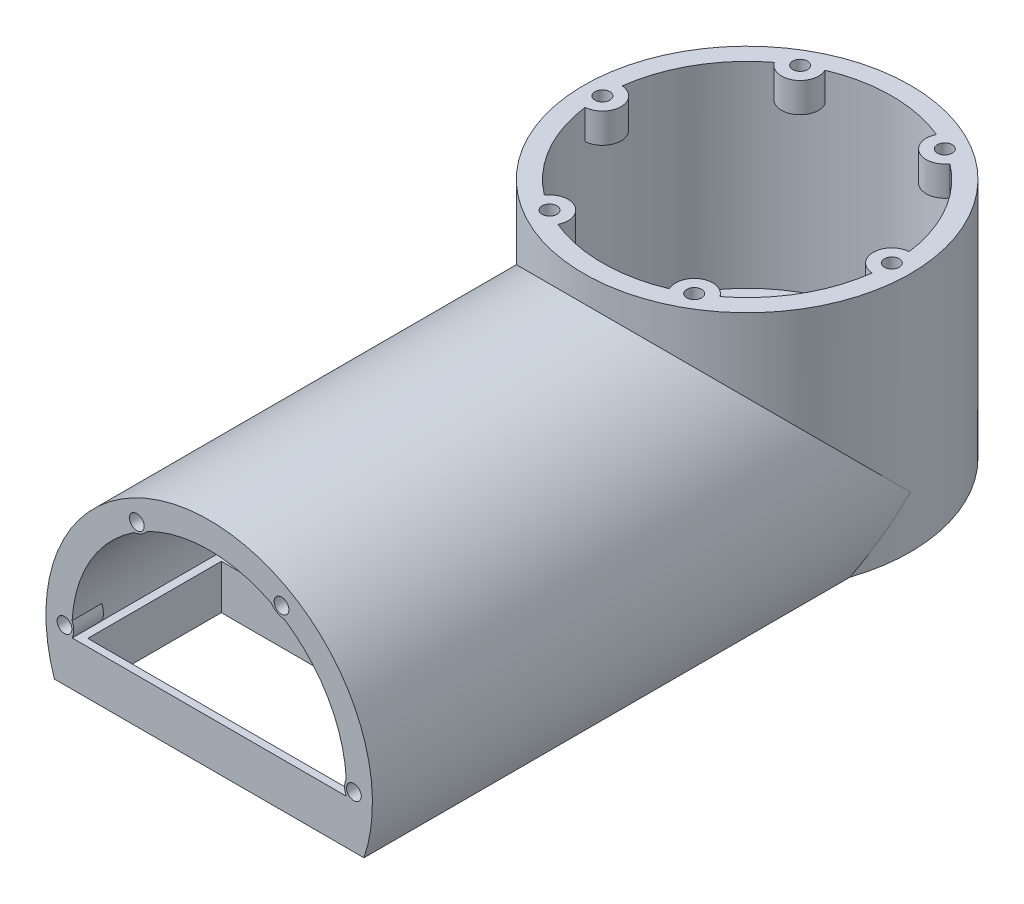
SolidWorks part; units mm, degrees
ref_plane "Спереди" through (0, 0, 0) normal (0, 0, 1) x (1, 0, 0)
ref_plane "Сверху" through (0, 0, 0) normal (0, 1, 0) x (1, 0, 0)
ref_plane "Справа" through (0, 0, 0) normal (1, 0, 0) x (0, 0, -1)
sketch "Эскиз6" plane through (0, 0, 0) normal (1, 0, 0) x (0, 0, -1)
  line L0 (26, 0) -> (44, 0)
  line L1 (0, 0) -> (0, 77.627) construction
  line L2 (44, 0) -> (44, 64.98)
  line L3 (44, 64.98) -> (39, 64.98)
  line L4 (39, 64.98) -> (39, 12)
  line L5 (39, 12) -> (0, 12)
  line L6 (0, 12) -> (0, 7)
  line L7 (0, 7) -> (26, 7)
  line L8 (26, 7) -> (26, 0)
  dimension "D1" = 5
  dimension "D2" = 26
  dimension "D3" = 64.98
  dimension "D4" = 44
  dimension "D5" = 7
revolve "Повернуть1" add sketch "Эскиз6" angle 360 about L1
sketch "Эскиз9" plane through (0, 0, 0) normal (0, 1, 0) x (1, 0, 0)
  circle A0 centre (0, 0) radius 3
  circle A1 centre (0, 0) radius 7 construction
  circle A2 centre (0, 7) radius 1.5
  circle A3 centre (7, 0) radius 1.5
  circle A4 centre (0, -7) radius 1.5
  circle A5 centre (-7, 0) radius 1.5
  point P15 (0, 0)
  dimension "D1" = 4
extrude "Вырез-Вытянуть1" cut sketch "Эскиз9" along normal up to surface (12 mm away) from offset 7 up to face at (0, 12, -39)
sketch "Эскиз25" plane through (0, 64.98, 0) normal (0, 1, 0) x (1, 0, 0)
  arc A0 (-38.6795, -4.9897) -> (-38.6795, 4.9897) centre (-39, 0) ccw
  circle A1 centre (0, 0) radius 39 construction
  circle A2 centre (0, 0) radius 39 construction
  arc A3 (-38.6795, 4.9897) -> (-38.6795, -4.9897) centre (0, 0) ccw
extrude "Бобышка-Вытянуть17" add sketch "Эскиз25" against normal blind 8
sketch "Эскиз26" plane through (0, 64.98, 0) normal (0, 1, 0) x (1, 0, 0)
  circle A0 centre (-39, 0) radius 2
  circle A1 centre (0, 0) radius 39 construction
  dimension "D1" = 4
extrude "Вырез-Вытянуть12" cut sketch "Эскиз26" against normal blind 5
pattern_circular "Круговой массив3" count 6 over 360 about axis through (0, 64.98, 0) along (0, -1, 0) of "Бобышка-Вытянуть17", "Вырез-Вытянуть12"
ref_plane "Плоскость1" through (0, 0, 45) normal (0, 0, 1) x (1, 0, 0)
sketch "Эскиз28" plane through (0, 0, 45) normal (0, 0, 1) x (1, 0, 0)
  line L0 (15.0185, 64.98) -> (-15.0185, 64.98) construction
  line L1 (0, 64.98) -> (0, 12)
  line L2 (44, 64.98) -> (-44, 64.98) construction
  line L4 (0, 8.2774) -> (0, 12)
  line L5 (-41.7191, -0.0026) -> (41.7191, -0.0026)
  line L6 (-36.947, 12) -> (36.947, 12)
  arc A0 (41.7191, -0.0026) -> (-41.7191, -0.0026) centre (0, 13.98) ccw
  arc A1 (36.947, 12) -> (-36.947, 12) centre (0, 13.98) ccw
  point P0 (0, 64.98)
  point P1 (0, 0)
  point P2 (0, 13.98)
  point P4 (0, 13.98)
  point P10 (-86.3563, 36.1377)
  dimension "D1" = 88
  dimension "D2" = 74
  dimension "D3" = 64.9826
  dimension "D4" = 51
  dimension "D5" = 12
extrude "Бобышка-Вытянуть18" add sketch "Эскиз28" along normal blind 100 and the other way up to surface contours A1 A0 L5 L6 region at (34.8604, 39.0624, 45) other way up to face at (0, 64.98, -44)
sketch "Эскиз29" plane through (0, 0, 45) normal (0, 0, 1) x (1, 0, 0)
  line L0 (-36.9468, 12) -> (36.9468, 12)
  line L1 (0, 0) -> (0, 64.98) construction
  line L3 (15.0185, 64.98) -> (-15.0185, 64.98) construction
  line L4 (-44, 13.98) -> (44, 13.98) construction
  arc A6 (-36.9468, 12) -> (36.9468, 12) centre (0, 13.9826) cw
  dimension "D1" = 12
  dimension "D2" = 37
  dimension "D3" = 13.9826
  dimension "D4" = 73.8937
ref_plane "Плоскость2" through (0, 7, 0) normal (0, -1, 0) x (-1, 0, 0)
extrude "Вырез-Вытянуть21" cut sketch "Эскиз29" against normal blind 45 contours A6 L0
sketch "Эскиз35" plane through (0, -0.0026, 0) normal (0, -1, 0) x (1, 0, 0)
  line L0 (0, 145) -> (0, 92.2743) construction
  line L1 (-41.7191, 145) -> (41.7191, 145) construction
  line L2 (-34.7191, 143) -> (-34.7191, 107)
  line L3 (-41.7191, 13.9826) -> (-41.7191, 145) construction
  line L4 (-34.7191, 143) -> (34.7191, 143)
  line L5 (34.7191, 143) -> (34.7191, 107)
  line L8 (-34.7191, 107) -> (34.7191, 107)
  point P19 (-34.7191, 101.335)
  dimension "D1" = 7
  dimension "D2" = 2
  dimension "D3" = 36
extrude "Вырез-Вытянуть25" cut sketch "Эскиз35" against normal blind 13
sketch "Эскиз33" plane through (0, 0, 145) normal (0, 0, 1) x (1, 0, 0)
  line L0 (0, 57.98) -> (0, 0) construction
  line L1 (-44, 13.98) -> (44, 13.98) construction
  circle A1 centre (-39, 13.98) radius 2
  arc A7 (-41.1795, 8.9903) -> (-41.1795, 18.9697) centre (-41.5, 13.98) ccw
  arc A8 (-41.1795, 8.9903) -> (-41.1795, 18.9697) centre (-2.5, 13.98) cw
  arc A9 (-44, 13.98) -> (-41.72, 0) centre (0, 13.98) ccw construction
  dimension "D1" = 4
  dimension "D3" = 2.5
  dimension "D2" = 39
extrude "Бобышка-Вытянуть24" add sketch "Эскиз33" against normal blind 8
extrude "Вырез-Вытянуть23" cut sketch "Эскиз33<2>" against normal blind 7 contours A1
sketch "Эскиз33<2>" plane through (0, 0, 145) normal (0, 0, 1) x (1, 0, 0) same geometry as "Эскиз33"
pattern_circular "Круговой массив4" count 4 every 60 about axis through (0, 13.98, 145) along (0, 0, 1) of "Вырез-Вытянуть23", "Бобышка-Вытянуть24" reverse direction yes
sketch "Эскиз34" plane through (0, -0.0026, 0) normal (0, -1, 0) x (1, 0, 0)
  line L0 (0, 145) -> (0, 106.1767) construction
  line L1 (-41.7191, 145) -> (41.7191, 145) construction
  circle A0 centre (-38, 141) radius 2.5
  circle A1 centre (-38, 109) radius 2.5
  circle A2 centre (38, 141) radius 2.5
  circle A3 centre (38, 109) radius 2.5
  dimension "D1" = 5
  dimension "D2" = 32
  dimension "D3" = 76
  dimension "D4" = 4
extrude "Вырез-Вытянуть24" cut sketch "Эскиз34" against normal blind 8
